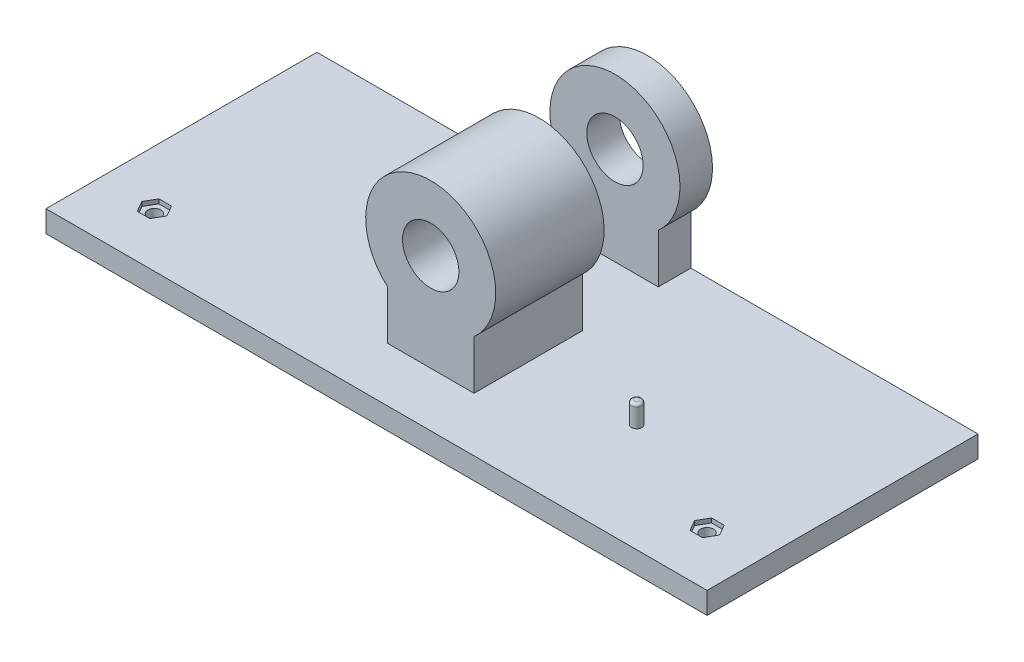
SolidWorks part; units mm, degrees
ref_plane "Front Plane" through (0, 0, 0) normal (0, 0, 1) x (1, 0, 0)
ref_plane "Top Plane" through (0, 0, 0) normal (0, 1, 0) x (1, 0, 0)
ref_plane "Right Plane" through (0, 0, 0) normal (1, 0, 0) x (0, 0, -1)
sketch "Sketch1" plane through (0, 0, 0) normal (0, 1, 0) x (1, 0, 0)
  line L0 (152.5, 125) -> (152.5, 0) construction
  line L1 (0, 0) -> (305, 0)
  line L2 (0, 0) -> (0, 125)
  line L3 (0, 125) -> (305, 125)
  line L4 (305, 0) -> (305, 125)
  line L5 (25, 100) -> (280, 100) construction
  line L6 (280, 25) -> (280, 100) construction
  line L7 (25, 25) -> (280, 25) construction
  line L8 (25, 25) -> (25, 100) construction
  line L9 (152.5, 62.5) -> (25, 62.5) construction
  line L10 (30.7735, 100) -> (27.8868, 105) construction
  line L11 (27.8868, 105) -> (22.1132, 105) construction
  line L12 (22.1132, 105) -> (19.2265, 100) construction
  line L13 (19.2265, 100) -> (22.1132, 95) construction
  line L14 (22.1132, 95) -> (27.8868, 95) construction
  line L15 (27.8868, 95) -> (30.7735, 100) construction
  line L16 (27.8868, 30) -> (30.7735, 25) construction
  line L17 (22.1132, 30) -> (27.8868, 30) construction
  line L18 (19.2265, 25) -> (22.1132, 30) construction
  line L19 (22.1132, 20) -> (19.2265, 25) construction
  line L20 (27.8868, 20) -> (22.1132, 20) construction
  line L21 (30.7735, 25) -> (27.8868, 20) construction
  line L22 (282.8868, 30) -> (277.1132, 30) construction
  line L23 (285.7735, 25) -> (282.8868, 30) construction
  line L24 (282.8868, 20) -> (285.7735, 25) construction
  line L25 (277.1132, 20) -> (282.8868, 20) construction
  line L26 (274.2265, 25) -> (277.1132, 20) construction
  line L27 (277.1132, 30) -> (274.2265, 25) construction
  line L28 (277.1132, 95) -> (274.2265, 100) construction
  line L29 (282.8868, 95) -> (277.1132, 95) construction
  line L30 (285.7735, 100) -> (282.8868, 95) construction
  line L31 (282.8868, 105) -> (285.7735, 100) construction
  line L32 (277.1132, 105) -> (282.8868, 105) construction
  line L33 (274.2265, 100) -> (277.1132, 105) construction
  line L34 (172.5, 75) -> (172.5, 125) construction
  line L35 (132.5, 0) -> (172.5, 0) construction
  line L36 (132.5, 0) -> (132.5, 125) construction
  line L37 (132.5, 125) -> (172.5, 125) construction
  line L38 (172.5, 0) -> (172.5, 125) construction
  line L39 (132.5, 75) -> (172.5, 75) construction
  line L40 (132.5, 75) -> (132.5, 25) construction
  line L41 (132.5, 25) -> (172.5, 25) construction
  line L42 (172.5, 75) -> (172.5, 25) construction
  line L50 (132.5, 75) -> (115, 75) construction
  line L52 (132.5, 75) -> (115, 62.5) construction
  line L53 (115, 62.5) -> (115, 87.5) construction
  circle A1 centre (25, 100) radius 5 construction
  circle A3 centre (280, 25) radius 3
  circle A4 centre (25, 25) radius 3
  circle A8 centre (115, 62.5) radius 3
  circle A9 centre (115, 87.5) radius 3
  dimension "D3" = 6
  dimension "D1" = 305
  dimension "D2" = 125
  dimension "D5" = 10
  dimension "D6" = 40
  dimension "D8" = 50
  dimension "D12" = 17.5
  dimension "D4" = 25
  dimension "D13" = 2
extrude "Boss-Extrude1" add sketch "Sketch1" along normal blind 10
sketch "Sketch6" plane through (0, 10, 0) normal (0, 1, 0) x (1, 0, 0)
  line L0 (152.5, 125) -> (152.5, 0) construction
  line L7 (305, 125) -> (0, 125) construction
  line L8 (0, 0) -> (305, 0) construction
  line L9 (152.5, 62.5) -> (0, 62.5) construction
  line L10 (0, 125) -> (0, 0) construction
  line L29 (27.8868, 30) -> (30.7735, 25)
  line L30 (274.2265, 25) -> (277.1132, 20)
  line L31 (277.1132, 20) -> (282.8868, 20)
  line L32 (282.8868, 20) -> (285.7735, 25)
  line L33 (285.7735, 25) -> (282.8868, 30)
  line L34 (282.8868, 30) -> (277.1132, 30)
  line L35 (277.1132, 30) -> (274.2265, 25)
  line L36 (22.1132, 30) -> (27.8868, 30)
  line L37 (19.2265, 25) -> (22.1132, 30)
  line L38 (22.1132, 20) -> (19.2265, 25)
  line L39 (27.8868, 20) -> (22.1132, 20)
  line L40 (30.7735, 25) -> (27.8868, 20)
  circle A0 centre (280, 25) radius 5 construction
  dimension "D1" = 10
extrude "Cut-Extrude1" cut sketch "Sketch6" against normal blind 2
sketch "Sketch7" plane through (0, 10, 0) normal (0, 1, 0) x (1, 0, 0)
  line L0 (0, 0) -> (305, 0) construction
  line L1 (132.5, 25) -> (172.5, 25)
  line L2 (132.5, 25) -> (132.5, 75)
  line L3 (132.5, 75) -> (172.5, 75)
  line L4 (172.5, 25) -> (172.5, 75)
  line L5 (152.5, 0) -> (152.5, 125) construction
  line L6 (305, 125) -> (0, 125) construction
  line L7 (172.5, 75) -> (172.5, 125) construction
  line L18 (132.5, 110) -> (172.5, 110)
  line L19 (132.5, 110) -> (132.5, 125)
  line L20 (132.5, 125) -> (172.5, 125)
  line L21 (172.5, 110) -> (172.5, 125)
  point P11 (152.5, 75)
  point P20 (152.5, 110)
  dimension "D1" = 40
  dimension "D2" = 50
  dimension "D4" = 15
extrude "Boss-Extrude2" add sketch "Sketch7" along normal blind 22.6393
sketch "Sketch11" plane through (0, 0, -25) normal (0, 0, 1) x (1, 0, 0)
  circle A0 centre (152.5, 55) radius 30
  circle A1 centre (152.5, 55) radius 13
  dimension "D1" = 60
  dimension "D2" = 26
extrude "Boss-Extrude3" add sketch "Sketch11" against normal up to surface (100 mm away) up to face at (152.5, 13.1598, -125)
ref_plane "Plane1" through (0, 0, -62.5) normal (0, 0, 1) x (1, 0, 0)
sketch "Sketch12" plane through (305, 0, 0) normal (1, 0, 0) x (0, 0, -1)
  line L0 (125, 85) -> (25, 85) construction
  line L1 (75, 10) -> (110, 10)
  line L2 (75, 10) -> (75, 85)
  line L3 (75, 85) -> (110, 85)
  line L4 (110, 10) -> (110, 85)
  line L6 (110, 32.6393) -> (110, 10) construction
extrude "Cut-Extrude2" cut sketch "Sketch12" against normal through all
sketch "Sketch13" plane through (0, 10, 0) normal (0, 1, 0) x (1, 0, 0)
  line L0 (222.5, 50) -> (172.5, 50) construction
  line L1 (172.5, 25) -> (172.5, 75) construction
  circle A1 centre (222.5, 50) radius 2.4
  dimension "D1" = 4.8
  dimension "D2" = 50
extrude "Boss-Extrude4" add sketch "Sketch13" along normal blind 10
sketch "Sketch14" plane through (0, 0, 0) normal (0, -1, 0) x (1, 0, 0)
  line L12 (120.7735, -87.5) -> (117.8868, -82.5)
  line L13 (120.7735, -62.5) -> (117.8868, -57.5)
  line L14 (117.8868, -57.5) -> (112.1132, -57.5)
  line L15 (112.1132, -57.5) -> (109.2265, -62.5)
  line L16 (109.2265, -62.5) -> (112.1132, -67.5)
  line L17 (112.1132, -67.5) -> (117.8868, -67.5)
  line L18 (117.8868, -67.5) -> (120.7735, -62.5)
  line L19 (117.8868, -82.5) -> (112.1132, -82.5)
  line L20 (112.1132, -82.5) -> (109.2265, -87.5)
  line L21 (109.2265, -87.5) -> (112.1132, -92.5)
  line L22 (112.1132, -92.5) -> (117.8868, -92.5)
  line L23 (117.8868, -92.5) -> (120.7735, -87.5)
  circle A0 centre (115, -62.5) radius 5 construction
  dimension "D1" = 10
  dimension "D3" = 15
  dimension "D2" = 2
fillet "Fillet1" radius 1.3 1 edges at (222.5, 20, -47.6)
extrude "Cut-Extrude3" cut sketch "Sketch14" against normal blind 4
equation "\"joint_width\"=4"
equation "\"D2@Sketch7\"=5"
equation "\"short_base_length\"=12.5"
equation "\"D2@Sketch1\"=\"short_base_length\""
equation "\"outer_diam_main_joint\"=6"
equation "\"D1@Sketch11\"=\"outer_diam_main_joint\""
equation "\"D1@Sketch7\"=\"outer_diam_main_joint\"-2"
equation "\"D1@Boss-Extrude2\"=(\"outer_diam_main_joint\"/2)+1.5cm-sqr((\"outer_diam_main_joint\"/2)^2-((\"outer_diam_main_joint\"-2)/2)^2)"
equation "\"D6@Sketch1\"=\"outer_diam_main_joint\"-2"
equation "\"pulleyside\"=1.5"
